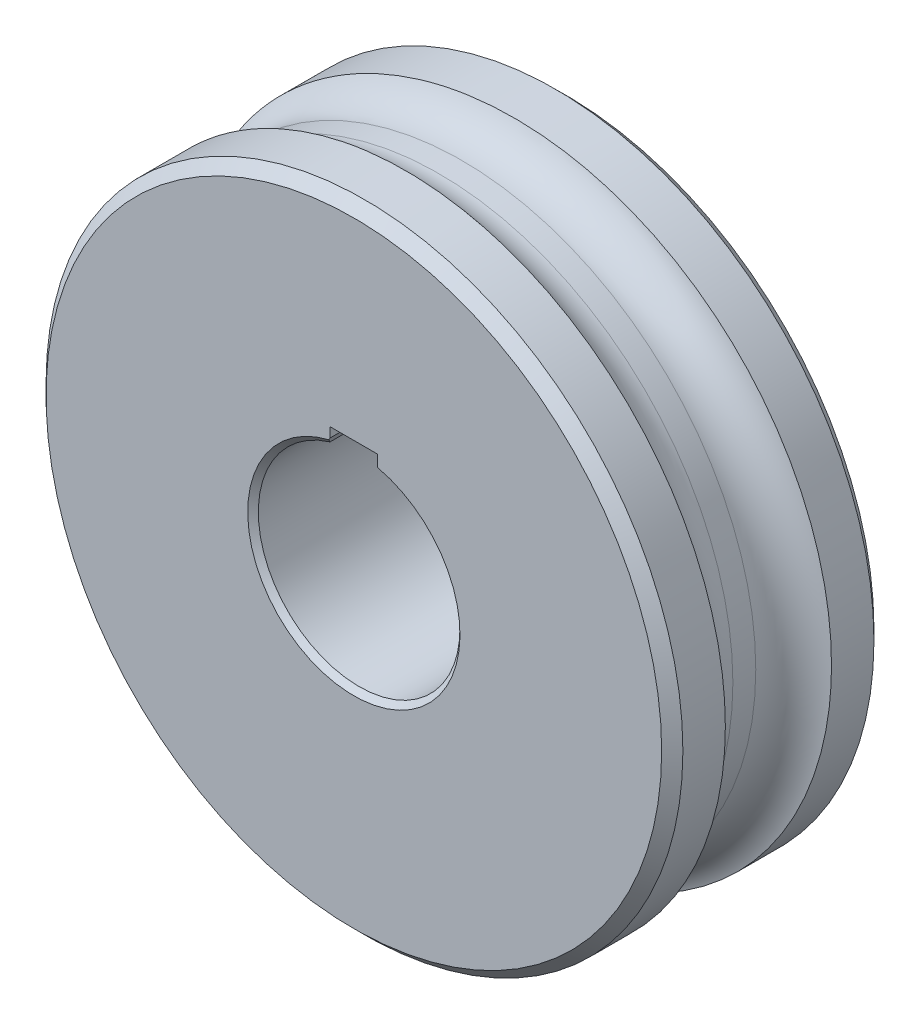
SolidWorks part; units mm, degrees
ref_plane "前视基准面" through (0, 0, 0) normal (0, 0, 1) x (1, 0, 0)
ref_plane "上视基准面" through (0, 0, 0) normal (0, 1, 0) x (1, 0, 0)
ref_plane "右视基准面" through (0, 0, 0) normal (1, 0, 0) x (0, 0, -1)
other "Configuration Table"
sketch "草图1" plane through (0, 0, 70.26) normal (0, 0, 1) x (1, 0, 0)
  circle A0 centre (-297.6709, 626.4154) radius 14.4381
  circle A1 centre (-297.6709, 626.4154) radius 60
extrude "凸台-拉伸1" add sketch "草图1" against normal up to surface (40 mm away)
ref_plane "基准面1" through (0, 0, 50.26) normal (0, 0, 1) x (1, 0, 0)
sketch "草图3" plane through (0, 0, 0) normal (0, 0, 1) x (1, 0, 0)
  point P0 (-297.6709, 626.4154)
ref_plane "基准面2" through (0, 626.4154, 0) normal (0, 1, 0) x (1, 0, 0)
sketch "草图4" plane through (0, 626.4154, 0) normal (0, 1, 0) x (1, 0, 0)
  line L0 (-316.0681, -48.1033) -> (-244.0953, -48.1033) construction
  line L1 (-244.0953, -48.1033) -> (-244.0953, -52.4167)
  line L2 (-237.6709, -40.26) -> (-237.6709, -60.26)
  line L3 (-299.4917, -70.26) -> (-299.4917, -4.8999) construction
  line L4 (-357.6709, -70.26) -> (-237.6709, -70.26) construction
  arc A0 (-237.6709, -40.26) -> (-244.0953, -48.1033) centre (-236.0953, -48.1033) ccw
  arc A1 (-237.6709, -40.26) -> (-244.0953, -48.1033) centre (-236.0953, -48.1033) ccw construction
  arc A2 (-237.6709, -60.26) -> (-244.0953, -52.4167) centre (-236.0953, -52.4167) cw
revolve "切除-旋转1" cut sketch "草图4" angle 360 about L3
chamfer "倒角1" distance 2 angle 45 2 edges at (-237.6709, 626.4154, 30.26) (-237.6709, 626.4154, 70.26)
sketch "草图5" plane through (0, 0, 70.26) normal (0, 0, 1) x (1, 0, 0)
  circle A0 centre (-297.6709, 626.4154) radius 25.1617
extrude "凸台-拉伸2" add sketch "草图5" against normal up to surface (40 mm away) up to face at (-239.6709, 626.4154, 30.26)
sketch "草图6" plane through (0, 0, 30.26) normal (0, 0, -1) x (-1, 0, 0)
  line L0 (293.1709, 648.0954) -> (302.1709, 648.0954)
  line L1 (293.1709, 648.0954) -> (293.1709, 626.4154)
  line L2 (293.1709, 626.4154) -> (302.1709, 626.4154)
  line L3 (302.1709, 626.4154) -> (302.1709, 648.0954)
  circle A0 centre (297.6709, 626.4154) radius 19
  dimension "D1" = 38
  dimension "D2" = 21.68
  dimension "D3" = 4.5
  dimension "D4" = 4.5
extrude "切除-拉伸1" cut sketch "草图6" against normal through all both and the other way through all contours L1 A0 L3 L2 | A0 L3 L0 L1 | L3 A0 L1 L2
chamfer "倒角2" distance 1 angle 45 4 edges at (-297.6709, 607.4154, 70.26) (-297.6709, 607.4154, 30.26) (-293.1709, 644.8748, 50.26) (-302.1709, 644.8748, 50.26)
